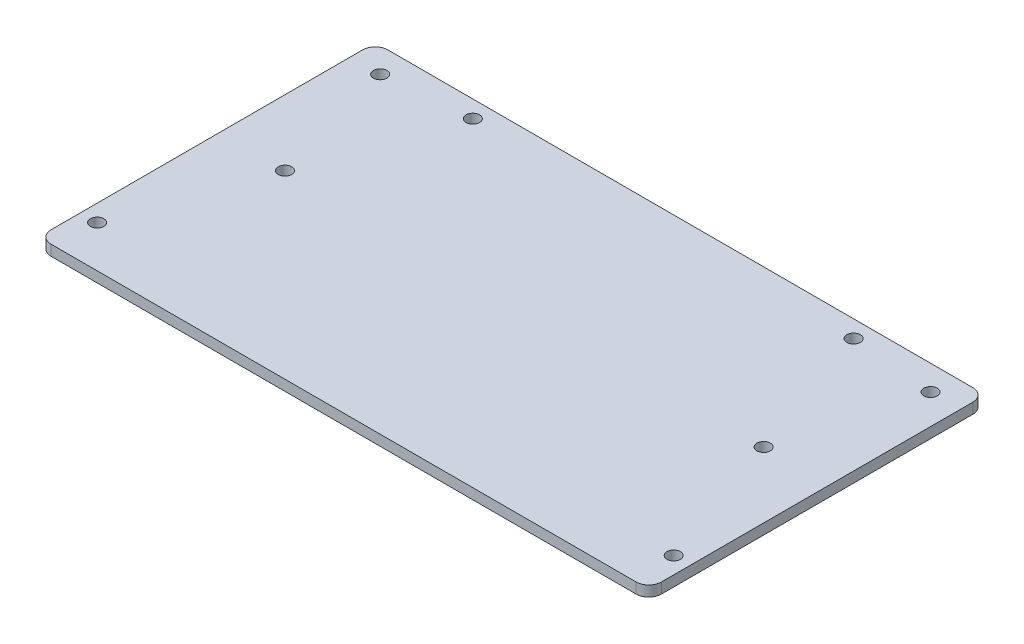
SolidWorks part; units mm, degrees
ref_plane "Front Plane" through (0, 0, 0) normal (0, 0, 1) x (1, 0, 0)
ref_plane "Top Plane" through (0, 0, 0) normal (0, 1, 0) x (1, 0, 0)
ref_plane "Right Plane" through (0, 0, 0) normal (1, 0, 0) x (0, 0, -1)
sketch "Sketch1" plane through (0, 0, 0) normal (0, 1, 0) x (1, 0, 0)
  line L0 (0, 0) -> (0, -101.6)
  line L1 (0, -101.6) -> (184.15, -101.6)
  line L2 (184.15, -101.6) -> (184.15, 0)
  line L3 (184.15, 0) -> (0, 0)
  dimension "D1" = 184.15
  dimension "D3" = 101.6
extrude "Boss-Extrude1" add sketch "Sketch1" along normal blind 3.175 contours L2 L3 L0 L1 region at (92.075, 0, 50.8)
fillet "Fillet1" radius 3.81 4 edges at (184.15, 1.5875, 0) (184.15, 1.5875, 101.6) (0, 1.5875, 0) (0, 1.5875, 101.6)
sketch "Sketch2" plane through (0, 3.175, 0) normal (0, 1, 0) x (1, 0, 0)
  line L0 (92.075, 0) -> (92.075, -101.6) construction
  line L1 (180.34, 0) -> (3.81, 0) construction
  line L2 (3.81, -101.6) -> (180.34, -101.6) construction
  circle A4 centre (5.0725, -89.0071) radius 2.032 construction
  circle A5 centre (5.0725, -89.0071) radius 2.032
  circle A6 centre (19.8456, -47.0839) radius 2.032 construction
  circle A7 centre (34.6187, -5.1607) radius 2.032 construction
  circle A8 centre (9.0348, -7.5315) radius 2.032 construction
  circle A9 centre (19.8456, -47.0839) radius 2.032
  circle A10 centre (34.6187, -5.1607) radius 2.032
  circle A11 centre (9.0348, -7.5315) radius 2.032
  circle A12 centre (179.0775, -89.0071) radius 2.032
  circle A13 centre (164.3044, -47.0839) radius 2.032
  circle A14 centre (175.1152, -7.5315) radius 2.032
  circle A15 centre (149.5313, -5.1607) radius 2.032
extrude "Cut-Extrude1" cut sketch "Sketch2" against normal through all contours A11 | A9 | A5 | A12 | A13 | A15 | A14 | A10 region at (5.0725, 3.175, 89.0071) region at (19.8456, 3.175, 47.0839) region at (9.0348, 3.175, 7.5315) region at (179.0775, 3.175, 89.0071) region at (164.3044, 3.175, 47.0839) region at (175.1152, 3.175, 7.5315) region at (149.5313, 3.175, 5.1607)
